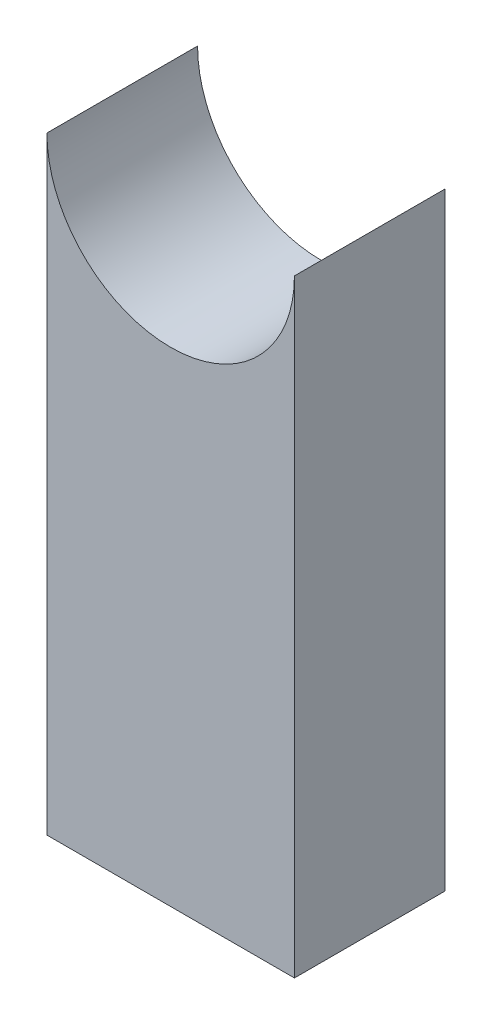
SolidWorks part; units mm, degrees
ref_plane "Front Plane" through (0, 0, 0) normal (0, 0, 1) x (1, 0, 0)
ref_plane "Top Plane" through (0, 0, 0) normal (0, 1, 0) x (1, 0, 0)
ref_plane "Right Plane" through (0, 0, 0) normal (1, 0, 0) x (0, 0, -1)
sketch "Sketch1" plane through (0, 0, 0) normal (0, 0, 1) x (1, 0, 0)
  line L0 (-14.605, 0) -> (-14.605, -71.755)
  line L1 (-14.605, -71.755) -> (14.605, -71.755)
  line L2 (14.605, -71.755) -> (14.605, 0)
  line L3 (0, -14.605) -> (0, -71.755) construction
  circle A0 centre (0, 0) radius 14.605 construction
  arc A1 (-14.605, 0) -> (13.9668, 4.2701) centre (0, 0) ccw
  dimension "D1" = 29.21
  dimension "D2" = 57.15
extrude "Boss-Extrude1" add sketch "Sketch1" along normal blind 17.78 contours A1 L0 L1 L2 region at (0, -41.5247, 0)
